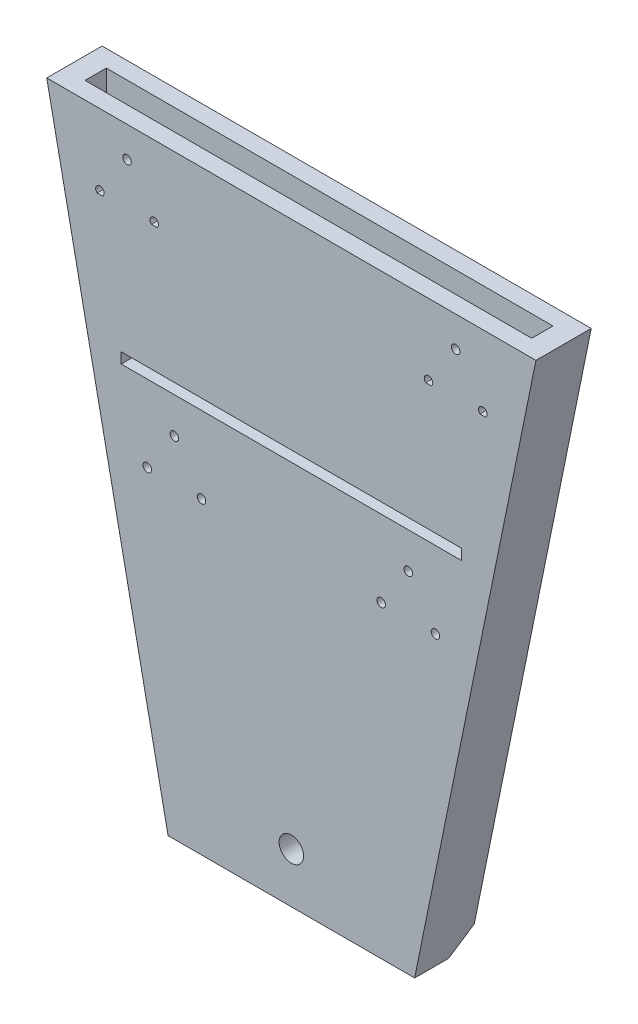
SolidWorks part; units mm, degrees
ref_plane "前视基准面" through (0, 0, 0) normal (0, 0, 1) x (1, 0, 0)
ref_plane "上视基准面" through (0, 0, 0) normal (0, 1, 0) x (1, 0, 0)
ref_plane "右视基准面" through (0, 0, 0) normal (1, 0, 0) x (0, 0, -1)
other "Configuration Table"
sketch "草图1" plane through (0, 0, 0) normal (0, 0, 1) x (1, 0, 0)
  line L0 (-60, 0) -> (60, 0)
  line L1 (0, 77.3448) -> (0, -71.5734) construction
  line L2 (-115, 270) -> (115, 270)
  line L3 (-115, 270) -> (-60, 0)
  line L4 (115, 270) -> (60, 0)
  point P3 (0, 0)
  point P8 (0, 270)
  dimension "D1" = 120
  dimension "D2" = 230
  dimension "D3" = 270
extrude "凸台-拉伸1" add sketch "草图1" along normal blind 8
sketch "草图2" plane through (0, 0, 8) normal (0, 0, 1) x (1, 0, 0)
  line L0 (-60, 0) -> (60, 0) construction
  line L1 (0, -1000) -> (0, 0.3) construction
  line L2 (0, 26.71) -> (0, 57.7278) construction
  line L3 (0.005, 0.31) -> (0, 0.3)
  line L4 (0, 26.71) -> (12.1089, 26.71)
  line L6 (0, 0.3) -> (17.4887, 0.3)
  line L7 (12.1089, 26.71) -> (17.4887, 0.3)
  line L8 (-115, 270) -> (-60, 0) construction
  arc A0 (0, 26.71) -> (0.005, 0.31) centre (0, 13.51) ccw
  dimension "D1" = 26.4
  dimension "D2" = 13.51
  dimension "D3" = 14.5
  dimension "D5" = 13.21
extrude "切除-拉伸1" cut sketch "草图2" against normal blind 8.6
sketch "草图3" plane through (0, 0, 8) normal (0, 0, 1) x (1, 0, 0)
  line L0 (-94.3261, 168.51) -> (94.3261, 168.51)
  line L1 (-115, 270) -> (-60, 0) construction
  line L2 (60, 0) -> (115, 270) construction
  line L4 (-96.3631, 178.51) -> (96.3631, 178.51)
  line L5 (-107.8704, 235) -> (107.8704, 235)
  point P0 (-115, 270)
  point P14 (0, 178.51)
  point P15 (0, 13.51)
  dimension "D1" = 155
  dimension "D2" = 10
  dimension "D3" = 35
sketch "草图5" plane through (0, 0, 0) normal (0, 0, -1) x (-1, 0, 0)
  line L4 (60, 0) -> (115, 270)
  line L5 (115, 270) -> (-115, 270)
  line L6 (-115, 270) -> (-60, 0)
  line L7 (-60, 0) -> (60, 0)
  line L8 (60, 0) -> (115, 270)
  line L9 (115, 270) -> (-115, 270)
  line L10 (-115, 270) -> (-60, 0)
  line L11 (-60, 0) -> (60, 0)
  dimension "D1" = 0
extrude "凸台-拉伸2" add sketch "草图5" along normal blind 8
sketch "草图6" plane through (0, 0, 8) normal (0, 0, 1) x (1, 0, 0)
  line L4 (-115, 270) -> (-60, 0)
  line L5 (-60, 0) -> (60, 0)
  line L6 (60, 0) -> (115, 270)
  line L7 (115, 270) -> (-115, 270)
  line L8 (-115, 270) -> (-60, 0)
  line L9 (-60, 0) -> (60, 0)
  line L10 (60, 0) -> (115, 270)
  line L11 (115, 270) -> (-115, 270)
  point P2 (0, 13.51)
  dimension "D1" = 0
extrude "凸台-拉伸3" add sketch "草图6" along normal blind 10
sketch "草图7" plane through (0, 0, 18) normal (0, 0, 1) x (1, 0, 0)
  circle A0 centre (0, 13.51) radius 5.75
  dimension "D1" = 11.5
extrude "切除-拉伸2" cut sketch "草图7" against normal blind 22
ref_plane "基准面1" through (0, 0, 18) normal (0, 0, 1) x (1, 0, 0)
sketch "草图9" plane through (0, 0, 18) normal (0, 0, 1) x (1, 0, 0)
  line L0 (-60, 0) -> (60, 0)
  line L1 (60, 0) -> (57.963, -10)
  line L2 (57.963, -10) -> (-57.963, -10)
  line L3 (-57.963, -10) -> (-60, 0)
  line L4 (60, 0) -> (115, 270) construction
  line L5 (-115, 270) -> (-60, 0) construction
  line L6 (60, 0) -> (115, 270)
  line L7 (-115, 270) -> (-60, 0)
  dimension "D1" = 10
extrude "凸台-拉伸5" add sketch "草图9" against normal blind 26 contours L3 L2 L1 L0 region at (0, -4.9712, 18)
ref_plane "基准面2" through (0, 0, -8) normal (0, 0, 1) x (1, 0, 0)
sketch "草图11" plane through (0, 0, -8) normal (0, 0, 1) x (1, 0, 0)
  line L0 (110.9179, 270) -> (53.8808, -10)
  line L1 (-110.9179, 270) -> (-53.8808, -10)
  line L2 (109.6932, 270) -> (52.6562, -10)
  line L3 (-109.6932, 270) -> (-52.6562, -10)
  line L4 (115, 270) -> (-115, 270)
  line L5 (-115, 270) -> (-57.963, -10)
  line L6 (-57.963, -10) -> (57.963, -10)
  line L7 (57.963, -10) -> (115, 270)
  line L8 (115, 270) -> (-115, 270)
  line L9 (-115, 270) -> (-57.963, -10)
  line L10 (-57.963, -10) -> (57.963, -10)
  line L11 (57.963, -10) -> (115, 270)
  dimension "D2" = 4
  dimension "D3" = 4
  dimension "D4" = 1.2
  dimension "D5" = 1.2
  dimension "D1" = 0
sketch "草图12" plane through (0, 0, -8) normal (0, 0, 1) x (1, 0, 0)
  line L0 (-115, 270) -> (-60, 0) construction
  line L1 (60, 0) -> (115, 270) construction
  line L2 (-115, 270) -> (-60, 0)
  line L3 (60, 0) -> (115, 270)
  line L4 (60, 0) -> (-60, 0)
  line L5 (57.963, -10) -> (60, 0)
  line L6 (-57.963, -10) -> (57.963, -10)
  line L7 (-60, 0) -> (-57.963, -10)
  line L8 (60, 0) -> (-60, 0)
  line L9 (57.963, -10) -> (60, 0)
  line L10 (-57.963, -10) -> (57.963, -10)
  line L11 (-60, 0) -> (-57.963, -10)
  line L12 (-109.6932, 270) -> (-52.6562, -10) construction
  line L13 (109.6932, 270) -> (52.6562, -10) construction
  line L14 (-110.9179, 270) -> (-53.8808, -10) construction
  line L15 (110.9179, 270) -> (53.8808, -10) construction
  line L16 (115, 270) -> (-115, 270)
  line L17 (-115, 270) -> (-57.963, -10)
  line L18 (-57.963, -10) -> (57.963, -10)
  line L19 (57.963, -10) -> (115, 270)
  line L20 (115, 270) -> (-115, 270)
  line L21 (-115, 270) -> (-57.963, -10)
  line L22 (-57.963, -10) -> (57.963, -10)
  line L23 (57.963, -10) -> (115, 270)
  line L24 (-109.6932, 270) -> (-52.6562, -10)
  line L25 (109.6932, 270) -> (52.6562, -10)
  line L26 (-110.9179, 270) -> (-53.8808, -10)
  line L27 (110.9179, 270) -> (53.8808, -10)
  dimension "D1" = 0
  dimension "D2" = 0
extrude "切除-拉伸4" cut sketch "草图12" along normal blind 21 contours L25 L8 L24 L22 region at (0, -4.9684, -8)
chamfer "倒角6" distance 5 angle 45 1 edges at (0, 0, -8)
chamfer "倒角8" distance 10 angle 45 2 edges at (-55.3096, -10, -8) (55.3096, -10, -8)
sketch "草图13" plane through (0, 270, 0) normal (0, 1, 0) x (1, 0, 0)
  line L1 (-105, 0) -> (105, 0)
  line L2 (-105, 0) -> (-105, -10)
  line L3 (-105, -10) -> (105, -10)
  line L4 (105, 0) -> (105, -10)
  line L5 (-105, 0) -> (105, -10) construction
  line L6 (-105, -10) -> (105, 0) construction
  line L7 (115, -18) -> (-115, -18) construction
  line L9 (-115, -18) -> (-115, 8) construction
  point P4 (0, -5)
  dimension "D1" = 210
  dimension "D2" = 10
  dimension "D3" = 13
  dimension "D4" = 115
extrude "切除-拉伸5" cut sketch "草图13" against normal blind 15
sketch "草图14" plane through (0, 0, 18) normal (0, 0, 1) x (1, 0, 0)
  line L0 (-96.3631, 178.51) -> (96.3631, 178.51) construction
  line L1 (-96.3631, 178.51) -> (96.3631, 178.51)
  line L2 (-94.3261, 168.51) -> (94.3261, 168.51) construction
  line L3 (-107.8704, 235) -> (107.8704, 235) construction
  line L4 (115, 270) -> (-115, 270)
  line L5 (-115, 270) -> (-57.963, -10)
  line L6 (-57.963, -10) -> (57.963, -10)
  line L7 (57.963, -10) -> (115, 270)
  line L8 (115, 270) -> (-115, 270)
  line L9 (-115, 270) -> (-57.963, -10)
  line L10 (-57.963, -10) -> (57.963, -10)
  line L11 (57.963, -10) -> (115, 270)
  line L12 (-94.3261, 168.51) -> (94.3261, 168.51)
  line L13 (-107.8704, 235) -> (107.8704, 235)
  line L14 (0, 270) -> (0, -10) construction
  line L15 (-80, 176.01) -> (80, 176.01)
  line L16 (-80, 176.01) -> (-80, 171.01)
  line L17 (-80, 171.01) -> (80, 171.01)
  line L18 (80, 176.01) -> (80, 171.01)
  line L19 (-80, 176.01) -> (80, 171.01) construction
  line L20 (-80, 171.01) -> (80, 176.01) construction
  point P14 (0, 173.51)
  dimension "D2" = 160
  dimension "D3" = 5
  dimension "D4" = 5
  dimension "D1" = 0
extrude "切除-拉伸6" cut sketch "草图14" against normal blind 10 contours L18 L15 L16 L17 region at (0, 173.51, 18)
sketch "草图16" plane through (0, 0, 18) normal (0, 0, 1) x (1, 0, 0)
  line L0 (0, 270) -> (0, -27.9065) construction
  line L2 (115, 270) -> (-115, 270) construction
  line L3 (-107.8704, 235) -> (107.8704, 235) construction
  line L4 (-94.3261, 168.51) -> (94.3261, 168.51) construction
  line L5 (-96.3631, 178.51) -> (96.3631, 178.51) construction
  line L6 (115, 270) -> (-115, 270)
  line L7 (-107.8704, 235) -> (107.8704, 235)
  line L8 (-94.3261, 168.51) -> (94.3261, 168.51)
  line L9 (-96.3631, 178.51) -> (96.3631, 178.51)
  line L11 (-90.2182, 178.51) -> (90.2182, 178.51)
  line L12 (-90.2182, 178.51) -> (-90.2182, 168.51)
  line L13 (-90.2182, 168.51) -> (90.2182, 168.51)
  line L14 (90.2182, 178.51) -> (90.2182, 168.51)
  line L15 (-90.2182, 178.51) -> (90.2182, 168.51) construction
  line L16 (-90.2182, 168.51) -> (90.2182, 178.51) construction
  circle A0 centre (-77.25, 255.6426) radius 2
  circle A1 centre (-90, 236.5) radius 2
  circle A2 centre (-64.5, 236.5) radius 2
  circle A3 centre (64.5, 236.5) radius 2
  circle A4 centre (90, 236.5) radius 2
  circle A5 centre (77.25, 255.6426) radius 2
  circle A6 centre (-55, 154.1526) radius 2
  circle A7 centre (-67.75, 135.01) radius 2
  circle A8 centre (-42.25, 135.01) radius 2
  circle A9 centre (42.25, 135.01) radius 2
  circle A10 centre (67.75, 135.01) radius 2
  circle A11 centre (55, 154.1526) radius 2
  point P15 (0, 173.51)
  dimension "D6" = 4
  dimension "D7" = 4
  dimension "D8" = 4
  dimension "D15" = 4
  dimension "D16" = 4
  dimension "D17" = 4
  dimension "D1" = 33.5
  dimension "D2" = 33.5
  dimension "D3" = 25.5
  dimension "D4" = 23
  dimension "D5" = 23
  dimension "D9" = 90
  dimension "D10" = 23
  dimension "D11" = 23
  dimension "D12" = 25.5
  dimension "D13" = 33.5
  dimension "D14" = 33.5
  dimension "D18" = 55
extrude "切除-拉伸7" cut sketch "草图16" against normal blind 10 contours A0 | A1 | A2 | A5 | A3 | A4 | A6 | A8 | A11 | A9 | A10 | A7 region at (-90, 236.6324, 18) region at (90, 236.6324, 18) region at (64.5, 236.6324, 18) region at (-64.5, 236.6324, 18) region at (-77.25, 255.6426, 18) region at (77.25, 255.6426, 18) region at (-55, 154.1526, 18) region at (-42.25, 135.01, 18) region at (42.25, 135.01, 18) region at (67.75, 135.01, 18) region at (55, 154.1526, 18)
sketch "草图17" plane through (0, 0, 18) normal (0, 0, 1) x (1, 0, 0)
  point P0 (-60.2489, 215.8027)
  point P2 (-96.3631, 178.51)
sketch "草图18" plane through (0, 0, 0) normal (0, -1, 0) x (1, 0, 0)
  line L4 (-54.6932, 13) -> (-54.6932, -3)
  line L5 (-54.6932, -3) -> (54.6932, -3)
  line L6 (54.6932, -3) -> (54.6932, 13)
  line L7 (54.6932, 13) -> (-54.6932, 13)
  line L8 (-54.6932, 13) -> (-54.6932, -3)
  line L10 (54.6932, -3) -> (54.6932, 13)
  line L11 (54.6932, 13) -> (-54.6932, 13)
  line L13 (-54.6932, -3) -> (54.6932, -3)
  dimension "D1" = 0
extrude "凸台-拉伸7" add sketch "草图18" along normal blind 2
chamfer "倒角10" distance 2 angle 45 1 edges at (0, -2, -3)
